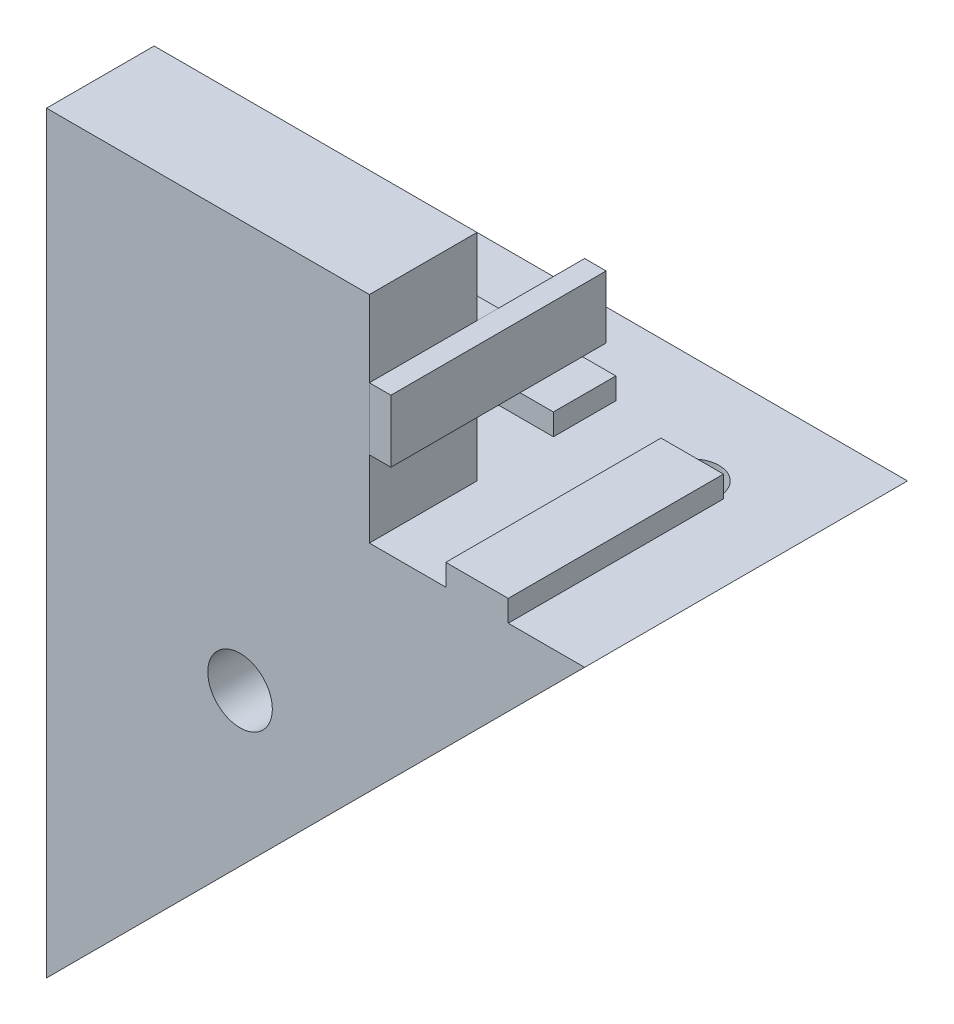
SolidWorks part; units mm, degrees
ref_plane "Front Plane" through (0, 0, 0) normal (0, 0, 1) x (1, 0, 0)
ref_plane "Top Plane" through (0, 0, 0) normal (0, 1, 0) x (1, 0, 0)
ref_plane "Right Plane" through (0, 0, 0) normal (1, 0, 0) x (0, 0, -1)
ref_plane "FrontPlane+10mm" through (0, 0, 10) normal (0, 0, 1) x (1, 0, 0)
sketch "Sketch1" plane through (0, 0, 0) normal (0, 0, 1) x (1, 0, 0)
  line L0 (-290, 0) -> (-10, 0) construction
  line L1 (0, 0) -> (-90, -90) construction
  line L2 (-10, 0) -> (0, 0) construction
  line L3 (-10, 0) -> (-10, 10) construction
  line L4 (-10, 10) -> (0, 10) construction
  line L5 (0, 0) -> (0, 10) construction
  line L6 (-90, -90) -> (-210, -90) construction
  line L7 (-300, 10) -> (-290, 10) construction
  line L8 (-300, 10) -> (-300, 0) construction
  line L9 (0, 0) -> (-10, 0)
  line L10 (-290, 10) -> (-290, 0) construction
  line L11 (-210, -90) -> (-300, 0) construction
  line L12 (-88.1335, -73.9914) -> (-16.0086, -1.8665) construction
  line L13 (-100, -80) -> (-90, -80) construction
  line L14 (-100, -80) -> (-100, -90) construction
  line L15 (-10, 0) -> (-10, 10)
  line L16 (-90, -80) -> (-90, -90) construction
  line L17 (-16.0086, -1.8665) -> (-8.9376, -8.9376) construction
  line L18 (-88.1335, -73.9914) -> (-81.0624, -81.0624) construction
  line L19 (-16.0086, -1.8665) -> (0, 0) construction
  line L20 (-88.1335, -73.9914) -> (-90, -90) construction
  line L21 (-10, 10) -> (-25, 10)
  line L22 (0, 0) -> (-8.9376, -8.9376)
  line L23 (-8.9376, -8.9376) -> (-16.0086, -1.8665)
  line L24 (-16.0086, -1.8665) -> (-25, -10.8579)
  line L25 (-25, -10.8579) -> (-25, 10)
  dimension "D1" = 10
  dimension "D2" = 10
  dimension "D3" = 300
  dimension "D4" = 10
  dimension "D5" = 120
  dimension "D6" = 135
  dimension "D7" = 45
  dimension "D8" = 45
  dimension "D9" = 127.2792
  dimension "D10" = 10
  dimension "D11" = 10
  dimension "D12" = 10
  dimension "D13" = 102
  dimension "D14" = 25
extrude "Main" add sketch "Sketch1" along normal blind 15
sketch "Sketch4" plane through (0, 0, 0) normal (0, 0, -1) x (-1, 0, 0)
  line L1 (10, 0) -> (25, 0)
  line L2 (10, 0) -> (10, 10)
  line L3 (10, 10) -> (25, 10)
  line L4 (25, 0) -> (25, 10)
extrude "Cut-Extrude2" cut sketch "Sketch4" against normal blind 10
sketch "Sketch2" plane through (0, 0, 10) normal (0, 0, -1) x (-1, 0, 0)
  line L0 (10, 0) -> (10, 10) construction
  line L1 (10, 6.45) -> (25, 6.45)
  line L2 (10, 6.45) -> (10, 3.55)
  line L3 (10, 3.55) -> (25, 3.55)
  line L4 (25, 6.45) -> (25, 3.55)
  line L5 (25, 0) -> (25, -10.8579) construction
  line L6 (10, 10) -> (25, 10) construction
  dimension "D1" = 3.55
  dimension "D2" = 2.9
extrude "Boss-Extrude3" add sketch "Sketch2" along normal blind 1
sketch "Sketch5" plane through (-7.0711, 7.0711, 0) normal (0.7071, -0.7071, 0) x (0, 0, -1)
  line L0 (-15, -25.3553) -> (0, -25.3553) construction
  line L1 (-3.55, -25.3553) -> (-6.45, -25.3553)
  line L2 (-3.55, -25.3553) -> (-3.55, -12.6396)
  line L3 (-3.55, -12.6396) -> (-6.45, -12.6396)
  line L4 (-6.45, -25.3553) -> (-6.45, -12.6396)
  line L5 (-15, -12.6396) -> (0, -12.6396) construction
  line L6 (0, -25.3553) -> (0, -12.6396) construction
  dimension "D1" = 3.55
  dimension "D2" = 2.9
extrude "Boss-Extrude4" add sketch "Sketch5" along normal blind 1
sketch "Sketch6" plane through (0, 0, 10) normal (0, 0, 1) x (1, 0, 0)
  line L0 (-25, -10.8579) -> (-16.0086, -1.8665)
  line L1 (-16.0086, -1.8665) -> (-8.9376, -8.9376)
  line L2 (-8.9376, -8.9376) -> (-25, -25)
  line L3 (-25, -10.8579) -> (-25, -25)
  line L4 (-12.4731, -5.402) -> (-19.5442, -12.4731) construction
  circle A0 centre (-16.0086, -8.9376) radius 1.5
  point P13 (-16.0086, -8.9376)
  dimension "D1" = 3
  dimension "D2" = 22.7157
  dimension "D3" = 14.1421
  dimension "D4" = 5
extrude "Boss-Extrude5" add sketch "Sketch6" along normal blind 5
sketch "Sketch7" plane through (0, 0, 10) normal (0, 0, -1) x (-1, 0, 0)
  line L0 (13.4984, -4.3767) -> (25, -15.8783)
  line L1 (25, -10.8579) -> (25, -25) construction
  line L3 (25, -15.8783) -> (25, -19.9795)
  line L4 (25, -19.9795) -> (11.4478, -6.4273)
  line L5 (11.4478, -6.4273) -> (13.4984, -4.3767)
  line L7 (8.9376, -8.9376) -> (16.0086, -1.8665) construction
  line L8 (16.0086, -1.8665) -> (8.9376, -8.9376) construction
  line L10 (25, -25) -> (0, 0) construction
  point P8 (15.2239, -13.4218)
  dimension "D1" = 2.9
  dimension "D2" = 3.55
extrude "Boss-Extrude6" add sketch "Sketch7" along normal blind 1
sketch "Sketch8" plane through (0, 0, 0) normal (0, 1, 0) x (1, 0, 0)
  line L0 (0, -15) -> (-10, -15) construction
  line L1 (-3.55, -15) -> (-6.45, -15)
  line L2 (-3.55, -15) -> (-3.55, -5)
  line L3 (-3.55, -5) -> (-6.45, -5)
  line L4 (-6.45, -15) -> (-6.45, -5)
  line L5 (0, -15) -> (0, 0) construction
  dimension "D1" = 3.55
  dimension "D2" = 2.9
  dimension "D3" = 10
extrude "Boss-Extrude7" add sketch "Sketch8" along normal blind 1
sketch "Sketch9" plane through (0, 0, 15) normal (0, 0, 1) x (1, 0, 0)
  line L0 (-10, 0) -> (-10, 10) construction
  line L1 (-10, 6.45) -> (-9, 6.45)
  line L2 (-10, 6.45) -> (-10, 3.55)
  line L3 (-10, 3.55) -> (-9, 3.55)
  line L4 (-9, 6.45) -> (-9, 3.55)
  line L5 (-10, 10) -> (-25, 10) construction
  dimension "D1" = 1
  dimension "D2" = 3.55
  dimension "D3" = 2.9
extrude "Boss-Extrude8" add sketch "Sketch9" against normal blind 10 separate body
sketch "Sketch11" plane through (0, 0, 0) normal (0, 1, 0) x (1, 0, 0)
  line L0 (0, -15) -> (0, 0) construction
  line L1 (0, 0) -> (-25, 0) construction
  circle A0 centre (-5, -5) radius 1.25
  dimension "D1" = 2.5
  dimension "D2" = 5
  dimension "D3" = 5
extrude "Cut-Extrude4" cut sketch "Sketch11" against normal through all
sketch "Sketch12" plane through (0, 0, 15) normal (0, 0, 1) x (1, 0, 0)
  circle A0 centre (-16.0086, -8.9376) radius 1.5
  arc A1 (-14.7117, -9.6913) -> (-16.7624, -7.6407) centre (-16.0086, -8.9376) ccw construction
extrude "Cut-Extrude5" cut sketch "Sketch12" against normal through all
sketch "Sketch13" plane through (0, 0, 0) normal (0, 1, 0) x (1, 0, 0)
  line L0 (-25, -10) -> (-25, 0) construction
  line L1 (-10, -3.55) -> (-25, -3.55)
  line L2 (-10, -3.55) -> (-10, -6.45)
  line L3 (-10, -6.45) -> (-25, -6.45)
  line L4 (-25, -3.55) -> (-25, -6.45)
  line L5 (0, -15) -> (0, 0) construction
  line L6 (0, 0) -> (-25, 0) construction
  dimension "D1" = 10
  dimension "D2" = 2.9
  dimension "D3" = 3.55
extrude "Boss-Extrude9" add sketch "Sketch13" along normal blind 1
ref_plane "Plane1" through (-30, 0, 0) normal (-1, 0, 0) x (0, 0, 1)
mirror "Mirror1" [suppressed] about plane through (-30, 0, 0) normal (-1, 0, 0) of bodies 115
sketch "Sketch14" plane through (-25, 0, -10) normal (1, 0, 0) x (0, 0, -1)
  line L1 (-26.8666, 14.682) -> (3.9245, 14.682)
  line L2 (-26.8666, 14.682) -> (-26.8666, -28.2083)
  line L3 (-26.8666, -28.2083) -> (3.9245, -28.2083)
  line L4 (3.9245, 14.682) -> (3.9245, -28.2083)
extrude "Cut-Extrude6" [suppressed] cut sketch "Sketch14" along normal through all
